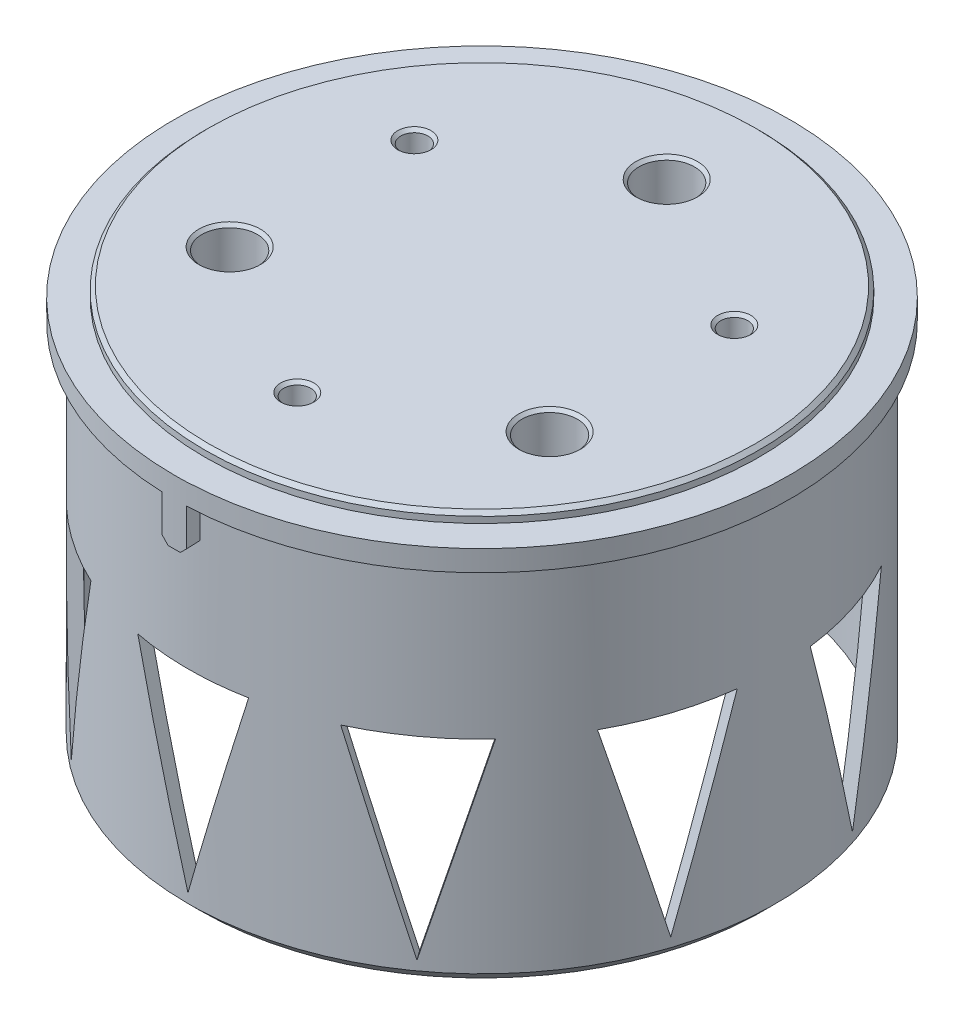
SolidWorks part; units mm, degrees
material "ABS"
ref_plane "Спереди" through (0, 0, 0) normal (0, 0, 1) x (1, 0, 0)
ref_plane "Сверху" through (0, 0, 0) normal (0, 1, 0) x (1, 0, 0)
ref_plane "Справа" through (0, 0, 0) normal (1, 0, 0) x (0, 0, -1)
sketch "Эскиз2" plane through (0, 0, 0) normal (0, 0, 1) x (1, 0, 0)
  line L0 (0, 0) -> (0, 74.988) construction
  line L1 (0, 0) -> (-47.75, 0)
  line L2 (-47.75, 0) -> (-47.75, -60)
  line L3 (-47.75, -60) -> (-45.75, -60)
  line L4 (-45.75, -60) -> (-45.75, -21)
  line L5 (-42.75, -18) -> (0, -18)
  line L6 (0, -18) -> (0, 0)
  arc A0 (-45.75, -21) -> (-42.75, -18) centre (-42.75, -21) cw
  dimension "D5" = 3
  dimension "D1" = 47.75
  dimension "D2" = 60
  dimension "D3" = 2
  dimension "D4" = 18
revolve "Основа" add sketch "Эскиз2" angle 360 about L0
sketch "Эскиз4" plane through (0, 0, 0) normal (0, 0, 1) x (1, 0, 0)
  line L0 (0, 0) -> (0, -40.75) construction
  line L1 (-9, -56.5) -> (9, -56.5) construction
  line L2 (-9, -56.5) -> (-9, -25) construction
  line L3 (-9, -25) -> (9, -25)
  line L4 (9, -56.5) -> (9, -25) construction
  line L5 (-9, -56.5) -> (9, -25) construction
  line L6 (-9, -25) -> (9, -56.5) construction
  line L7 (-42.75, -18) -> (42.75, -18) construction
  line L8 (-9, -25) -> (0, -56.5)
  line L9 (0, -56.5) -> (9, -25)
  line L10 (-42.75, -18) -> (42.75, -18) construction
  line L11 (-47.75, -60) -> (47.75, -60) construction
  line L12 (-47.75, -60) -> (47.75, -60) construction
  point P0 (0, -40.75)
  dimension "D1" = 3.5
  dimension "D2" = 18
  dimension "D3" = 7
  dimension "D4" = 31.891
  dimension "D6" = 74.055
extrude "Вырез облегчение" cut sketch "Эскиз4" against normal mid plane 141.7
pattern_circular "Массив вырезов" count 5 over 360 about axis through (0, 0, 0) along (0, -1, 0) of "Вырез облегчение"
sketch "Эскиз7" plane through (0, 0, 0) normal (0, 1, 0) x (1, 0, 0)
  circle A0 centre (0, 0) radius 50
  dimension "D1" = 100
extrude "Бобышка-Вытянуть1" add sketch "Эскиз7" along normal blind 5
sketch "Эскиз8" plane through (0, 5, 0) normal (0, 1, 0) x (1, 0, 0)
  circle A0 centre (0, 0) radius 45
  circle A1 centre (0, 0) radius 50 construction
  circle A2 centre (0, 0) radius 50
  dimension "D1" = 90
extrude "Вырез-Вытянуть1" cut sketch "Эскиз8" against normal blind 1.6
sketch "Эскиз9" plane through (0, 5, 0) normal (0, 1, 0) x (1, 0, 0)
  circle A0 centre (0, 0) radius 6
  dimension "D1" = 12
extrude "Вырез-Вытянуть2" [suppressed] cut sketch "Эскиз9" against normal through all
sketch "Эскиз10" plane through (0, 5, 0) normal (0, 1, 0) x (1, 0, 0)
  circle A0 centre (0, 30) radius 4.5
  circle A1 centre (0, -30) radius 2.2
  circle A2 centre (25.9808, -15) radius 4.5
  circle A3 centre (-25.9808, 15) radius 2.2
  circle A4 centre (-25.9808, -15) radius 4.5
  circle A5 centre (25.9808, 15) radius 2.2
  point P15 (0, 0)
  dimension "D1" = 9
  dimension "D3" = 4.4
  dimension "D2" = 30
  dimension "D4" = 30
  dimension "D5" = 3
extrude "Вырез-Вытянуть4" cut sketch "Эскиз10" against normal through all contours A0 | A4 | A2
extrude "Вырез-Вытянуть5" cut sketch "Эскиз10<4>" against normal blind 8 contours A3 | A5 | A1
sketch "Эскиз10<4>" plane through (0, 5, 0) normal (0, 1, 0) x (1, 0, 0) same geometry as "Эскиз10"
chamfer "Фаска1" distance 0.5 angle 45 6 edges at (25.9808, 5, 19.5) (0, 5, -25.5) (-25.9808, 5, 19.5) (0, 5, 32.2) (25.9808, 5, -12.8) (-25.9808, 5, -12.8)
chamfer "Фаска2" [suppressed] distance 0.5 angle 45
chamfer "Фаска3" [suppressed] distance 5 angle 45
sketch "Эскиз13" plane through (0, 0, 0) normal (0, -1, 0) x (1, 0, 0)
  line L0 (0, 0) -> (0, -50) construction
  line L1 (-1.91, -47.7118) -> (-2, -49.96)
  line L2 (1.91, -47.7118) -> (2, -49.96)
  line L3 (0, 0) -> (-8.7734, 0) construction
  line L4 (1.91, 47.7118) -> (2, 49.96)
  line L5 (-1.91, 47.7118) -> (-2, 49.96)
  circle A0 centre (0, 0) radius 50 construction
  arc A1 (-2, -49.96) -> (2, -49.96) centre (0, 0) ccw
  arc A2 (-1.91, -47.7118) -> (1.91, -47.7118) centre (0, 0) ccw
  circle A3 centre (0, 0) radius 47.75 construction
  circle A4 centre (0, 0) radius 47.75 construction
  arc A5 (-1.91, 47.7118) -> (1.91, 47.7118) centre (0, 0) cw
  arc A6 (-2, 49.96) -> (2, 49.96) centre (0, 0) cw
  circle M4 centre (0, 0) radius 47.75
  circle M5 centre (0, 0) radius 50
  dimension "D1" = 4
extrude "Бобышка-Вытянуть2" add sketch "Эскиз13" along normal blind 7 contours L5 L4 M4 M5 region at (0, 0, 48.8706)
chamfer "Фаска4" distance 1 angle 45 2 edges at (-1.955, -7, 48.8359) (1.955, -7, 48.8359)
chamfer "Фаска5" distance 2 angle 45 1 edges at (0, -60, -47.75)
chamfer "Фаска6" distance 5 angle 45 3 edges at (-25.9808, -18, 19.5) (0, -18, -25.5) (25.9808, -18, 19.5)
chamfer "Фаска7" distance 0.6 angle 45 1 edges at (0, 5, 45)
